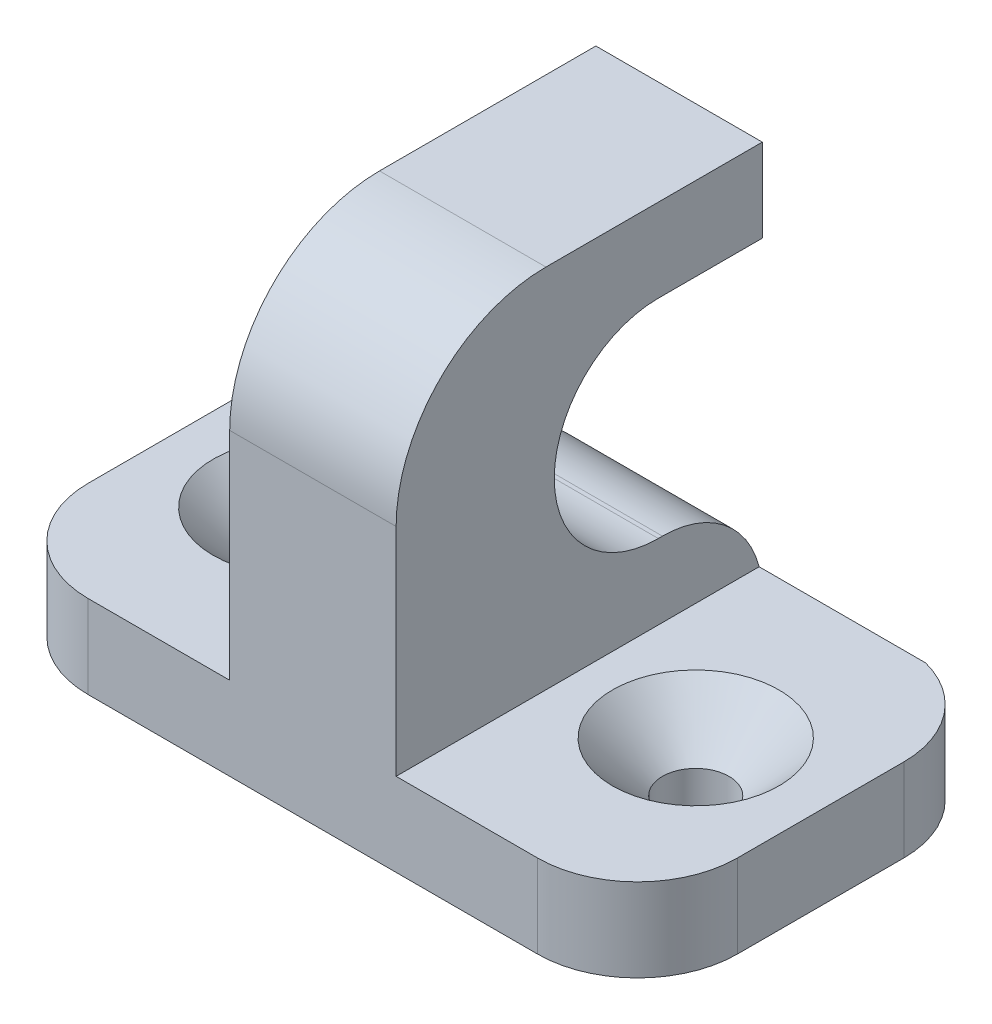
SolidWorks part; units mm, degrees
ref_plane "Front Plane" through (0, 0, 0) normal (0, 0, 1) x (1, 0, 0)
ref_plane "Top Plane" through (0, 0, 0) normal (0, 1, 0) x (1, 0, 0)
ref_plane "Right Plane" through (0, 0, 0) normal (1, 0, 0) x (0, 0, -1)
sketch "Sketch1" plane through (0, 0, 0) normal (0, 1, 0) x (1, 0, 0)
  line L1 (-19.5, 11) -> (19.5, 11)
  line L2 (-19.5, 11) -> (-19.5, -11)
  line L3 (-19.5, -11) -> (19.5, -11)
  line L4 (19.5, 11) -> (19.5, -11)
  line L5 (-19.5, 11) -> (19.5, -11) construction
  line L6 (-19.5, -11) -> (19.5, 11) construction
  point P0 (0, 0)
  dimension "D1" = 22
  dimension "D2" = 39
extrude "Boss-Extrude1" add sketch "Sketch1" along normal blind 5 contours L1 L4 L3 L2
sketch "Sketch2" plane through (0, 5, 0) normal (0, 1, 0) x (1, 0, 0)
  line L0 (-19.5, -11) -> (19.5, -11) construction
  line L1 (-5, 11) -> (5, 11)
  line L2 (-5, 11) -> (-5, -11)
  line L3 (-5, -11) -> (5, -11)
  line L4 (5, 11) -> (5, -11)
  line L5 (-5, 11) -> (5, -11) construction
  line L6 (-5, -11) -> (5, 11) construction
  point P0 (0, 0)
  dimension "D1" = 10
extrude "Boss-Extrude2" add sketch "Sketch2" along normal blind 22
sketch "Sketch3" plane through (0, 0, -11) normal (0, 0, -1) x (-1, 0, 0)
  line L0 (-5, 27) -> (-5, 5) construction
  line L1 (-5, 22) -> (5, 22)
  line L2 (-5, 22) -> (-5, 9.5)
  line L3 (-5, 9.5) -> (5, 9.5)
  line L4 (5, 22) -> (5, 9.5)
  line L5 (5, 27) -> (5, 5) construction
  line L6 (-5, 27) -> (5, 27) construction
  dimension "D1" = 12.5
  dimension "D2" = 5
extrude "Cut-Extrude1" cut sketch "Sketch3" against normal blind 12.5
fillet "Fillet1" radius 6.25 2 edges at (0, 22, 1.5) (0, 9.5, 1.5)
fillet "Fillet2" radius 6 4 edges at (-19.5, 2.5, 11) (19.5, 2.5, 11) (19.5, 2.5, -11) (-19.5, 2.5, -11)
fillet "Fillet3" radius 9 1 edges at (0, 27, 11)
sketch "Sketch4" plane through (0, 5, 0) normal (0, 1, 0) x (1, 0, 0)
  line L0 (-24.8822, 0) -> (23.9237, 0) construction
  line L1 (0, 14.4922) -> (0, -14.4156) construction
sketch "Sketch5" plane through (0, 5, 0) normal (0, 1, 0) x (1, 0, 0)
  line L0 (-24.8822, 0) -> (23.9237, 0) construction
  line L1 (0, 14.4922) -> (0, -14.4156) construction
  circle A0 centre (-12, 0) radius 2
  circle A1 centre (12, 0) radius 2
  dimension "D1" = 12
  dimension "D2" = 12
extrude "Cut-Extrude3" cut sketch "Sketch5" against normal through all
fillet "Fillet4" radius 6 1 edges at (0, 9.5, -11)
chamfer "Chamfer4" distance 3 angle 45 2 edges at (12, 5, 2) (-12, 5, 2)
